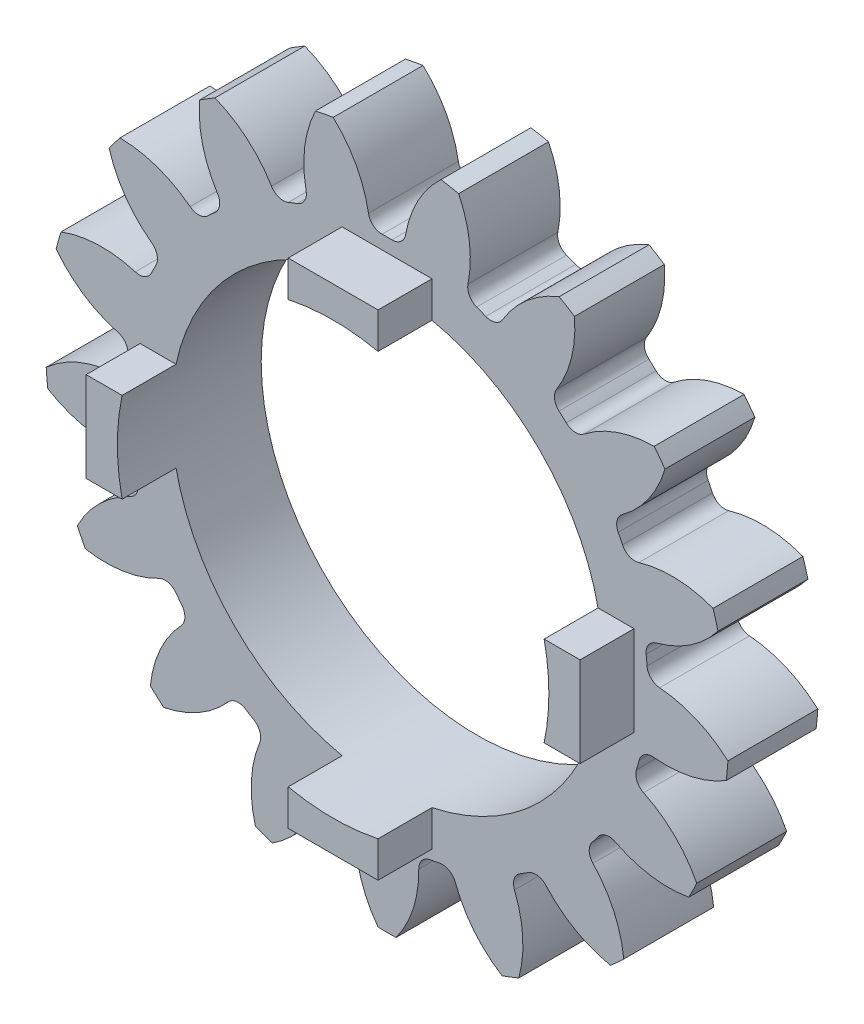
SolidWorks part; units mm, degrees
ref_plane "Front Plane" through (0, 0, 0) normal (0, 0, 1) x (1, 0, 0)
ref_plane "Top Plane" through (0, 0, 0) normal (0, 1, 0) x (1, 0, 0)
ref_plane "Right Plane" through (0, 0, 0) normal (1, 0, 0) x (0, 0, -1)
sketch "Sketch1" plane through (0, 0, 0) normal (0, 0, 1) x (1, 0, 0)
  line L4 (-0.9556, 14.4685) -> (0, 0) construction
  line L5 (0, 0) -> (0, 19) construction
  line L6 (0, 0) -> (3.4912, 18.6765) construction
  line L7 (-1.6208, 16.9226) -> (0.7345, 18.0445) construction
  line L8 (-1.6208, 16.9226) -> (0.3951, 17.1156) construction
  line L11 (1.6208, 16.9226) -> (-1.6208, 16.9226) construction
  circle A0 centre (0, 0) radius 14.5
  circle A1 centre (0, 0) radius 17 construction
  circle A2 centre (0, 0) radius 19
  arc A3 (-2.9986, 18.7619) -> (-0.9556, 14.4685) centre (-7.38, 14.0442) cw
  arc A4 (2.9986, 18.7619) -> (0.9556, 14.4685) centre (7.38, 14.0442) ccw
  point P5 (-17, 0)
  point P6 (-19, 0)
  point P7 (-14.5, 0)
  point P12 (-1.6208, 16.9226)
  point P22 (1.6208, 16.9226)
  dimension "D5" = 34
  dimension "D1" = 2.5
  dimension "D2" = 2
  dimension "D3" = 20
  dimension "D4" = 3.2416
  dimension "D6" = 10.588
  dimension "D7" = 0.5
extrude "Boss-Extrude1" add sketch "Sketch1" against normal blind 5 contours A2
extrude "Cut-Extrude1" cut sketch "Sketch1<4>" against normal blind 10 contours A4 A2 A3 A0 region at (0, 17.1672, 0)
sketch "Sketch1<4>" plane through (0, 0, 0) normal (0, 0, 1) x (1, 0, 0) same geometry as "Sketch1"
fillet "Fillet2" radius 0.76 2 edges at (0.9556, 14.4685, -2.5) (-0.9556, 14.4685, -2.5)
ref_axis "Axis1" through (0, 0, 0) along (0, 0, 1)
pattern_circular "CirPattern2" count 17 over 360 about axis through (0, 0, 0) along (0, 0, 1) of "Cut-Extrude1", "Fillet2"
sketch "Sketch2" plane through (0, 0, 0) normal (0, 0, 1) x (1, 0, 0)
  circle A0 centre (0, 0) radius 12
  dimension "D1" = 24
extrude "Cut-Extrude2" cut sketch "Sketch2" against normal up to surface (5 mm away) up to face at (0, 0, -5)
sketch "Sketch3" plane through (0, 0, 0) normal (0, 0, 1) x (1, 0, 0)
  line L0 (-2.5, 11.7367) -> (-2.5, 13.7367)
  line L1 (-2.5, 13.7367) -> (2.5, 13.7367)
  line L2 (2.5, 13.7367) -> (2.5, 11.7367)
  line L3 (0, 0) -> (0, 12) construction
  line L4 (13.7367, -2.5) -> (11.7367, -2.5)
  line L5 (13.7367, 2.5) -> (13.7367, -2.5)
  line L6 (11.7367, 2.5) -> (13.7367, 2.5)
  line L7 (-2.5, -13.7367) -> (-2.5, -11.7367)
  line L8 (2.5, -13.7367) -> (-2.5, -13.7367)
  line L9 (2.5, -11.7367) -> (2.5, -13.7367)
  line L10 (-13.7367, 2.5) -> (-11.7367, 2.5)
  line L11 (-13.7367, -2.5) -> (-13.7367, 2.5)
  line L12 (-11.7367, -2.5) -> (-13.7367, -2.5)
  circle A0 centre (0, 0) radius 12 construction
  arc A1 (-2.5, 11.7367) -> (2.5, 11.7367) centre (0, 0) cw
  arc A2 (11.7367, 2.5) -> (11.7367, -2.5) centre (0, 0) cw
  arc A3 (2.5, -11.7367) -> (-2.5, -11.7367) centre (0, 0) cw
  arc A4 (-11.7367, -2.5) -> (-11.7367, 2.5) centre (0, 0) cw
  point P24 (0, 0)
  dimension "D4" = 4
  dimension "D1" = 2.5
  dimension "D2" = 2.5
  dimension "D3" = 2
extrude "Boss-Extrude2" add sketch "Sketch3" along normal blind 3
equation "\"backlash\"= 0.1mm"
equation "\"module\"= 2mm"
equation "\"pressureAngle\"= 20deg"
equation "\"width\"= 10mm"
equation "\"D1@Sketch1\"= 1.25 * \"module\""
equation "\"D2@Sketch1\"=\"module\""
equation "\"D5@Sketch1\"=\"module\"*\"numberOfTeeth\""
equation "\"D1@Boss-Extrude1\"=\"width\"-5"
equation "\"D3@Sketch1\"=\"pressureAngle\""
equation "\"D1@Cut-Extrude1\"=\"width\""
equation "\"D1@CirPattern2\"=\"numberOfTeeth\""
equation "\"D1@Fillet2\"=0.38*\"module\""
equation "\"D4@Sketch1\"=pi*\"module\"/2+\"backlash\""
equation "\"numberOfTeeth\"= 17"
equation "\"D6@Sketch1\"=180/\"numberOfTeeth\""
equation "\"toothTipProfile\"= 1mm"
equation "\"D7@Sketch1\"=\"toothTipProfile\"/2"
equation "\"lengthOverallRack\"= pi * \"module\" * \"numberOfTeethRack\""
equation "\"numberOfTeethRack\"= 20"
